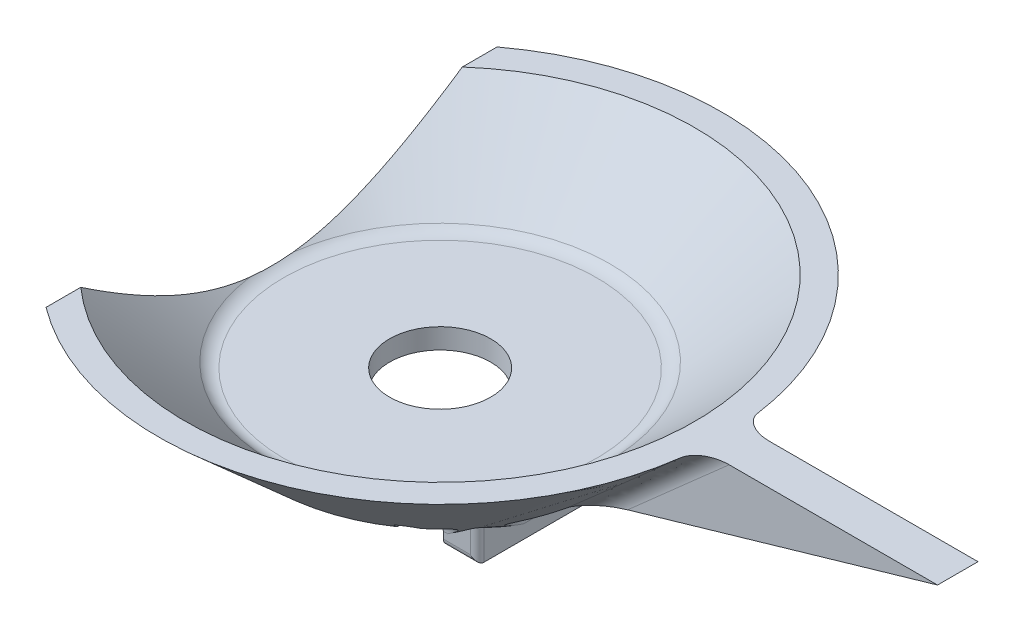
SolidWorks part; units mm, degrees
material "ABS"
ref_plane "前视基准面" through (0, 0, 0) normal (0, 0, 1) x (1, 0, 0)
ref_plane "上视基准面" through (0, 0, 0) normal (0, 1, 0) x (1, 0, 0)
ref_plane "右视基准面" through (0, 0, 0) normal (1, 0, 0) x (0, 0, -1)
other "Configuration Table"
sketch "草图1" plane through (0, 0, 0) normal (0, 1, 0) x (1, 0, 0)
  circle A0 centre (0, 0) radius 41.75
  circle A1 centre (0, 0) radius 37.75
  dimension "D1" = 4
  dimension "D2" = 83.5
ref_plane "基准面1" through (0, -15, 0) normal (0, 1, 0) x (1, 0, 0)
sketch "草图2" plane through (0, -15, 0) normal (0, 1, 0) x (1, 0, 0)
  circle A0 centre (0, 0) radius 25
  circle A1 centre (0, 0) radius 21
  dimension "D1" = 50
  dimension "D2" = 4
sketch "草图3" plane through (0, 0, 0) normal (0, 0, 1) x (1, 0, 0)
  line L0 (0, -15) -> (0, 0) construction
  line L1 (25, -15) -> (-25, -15) construction
  line L2 (41.75, 0) -> (37.75, 0)
  line L3 (41.75, 0) -> (-41.75, 0) construction
  line L4 (37.75, 0) -> (24.35, -12)
  line L5 (24.35, -12) -> (7.5, -12)
  line L6 (7.5, -12) -> (7.5, -15)
  line L7 (7.5, -15) -> (25, -15)
  line L8 (25, -15) -> (41.75, 0)
  dimension "D1" = 4
  dimension "D2" = 15
  dimension "D3" = 3
  dimension "D4" = 83.5
  dimension "D5" = 50
revolve "旋转1" add sketch "草图3" angle 360 about L0
sketch "草图4" plane through (0, 0, 0) normal (0, 0, 1) x (1, 0, 0)
  line L0 (41.75, 0) -> (76.75, 0)
  line L1 (76.75, 0) -> (25, -15)
  line L2 (25, -15) -> (22, -15)
  line L3 (-25, -15) -> (25, -15) construction
  line L4 (22, -15) -> (22, 0)
  line L5 (41.75, 0) -> (-41.75, 0) construction
  line L6 (22, 0) -> (41.75, 0)
  dimension "D1" = 3
  dimension "D2" = 35
extrude "凸台-拉伸1" add sketch "草图4" along normal mid plane 6
sketch "草图5" plane through (0, 0, 0) normal (0, 0, 1) x (1, 0, 0)
  line L15 (-24.35, -12) -> (-37.75, 0)
  line L16 (-24.35, -12) -> (-37.75, 0)
  line L17 (-37.75, 0) -> (0, 0)
  line L18 (0, 0) -> (0, -12)
  line L19 (0, -12) -> (-24.35, -12)
revolve "切除-旋转1" cut sketch "草图5" angle 360 about L18
fillet "圆角1" radius 3 3 edges at (0, -12, -24.35)
sketch "草图6" plane through (0, 0, 0) normal (0, 1, 0) x (1, 0, 0)
  line L0 (0, 0) -> (-25, 0) construction
  line L1 (-25, 45) -> (-25, -45)
  line L3 (-25, -45) -> (-45, -45)
  line L4 (-25, -45) -> (-25, 45)
  line L5 (-25, 45) -> (-45, 45)
  line L6 (-45, -45) -> (-45, 45)
  point P6 (-25, 0)
  circle M5 centre (0, 0) radius 37.75
  arc M6 (41.3555, 5.7255) -> (41.3555, -5.7255) centre (0, 0) ccw
  dimension "D1" = 25
  dimension "D2" = 90
  dimension "D3" = 20
extrude "切除-拉伸1" cut sketch "草图6" against normal through all contours L1 M6 M5 | L1 L4 M5 | L6 L3 L1 L5 M6 region at (-25.922, 0, -39.2187) region at (-25.6894, 0, -30.8614) region at (-30.1819, 0, 0)
sketch "草图7" plane through (0, -15, 0) normal (0, -1, 0) x (1, 0, 0)
  line L0 (0, 0) -> (0, 25) construction
  line L1 (-17.7, 0) -> (17.7, 0) construction
  line L3 (-20.2, 14.7296) -> (-15.2, 14.7296)
  line L4 (-20.2, 14.7296) -> (-20.2, -14.7296)
  line L5 (-20.2, -14.7296) -> (-15.2, -14.7296)
  line L6 (-15.2, 14.7296) -> (-15.2, -14.7296)
  line L7 (-20.2, 14.7296) -> (-15.2, -14.7296) construction
  line L8 (-20.2, -14.7296) -> (-15.2, 14.7296) construction
  line L9 (15.2, 14.7296) -> (20.2, 14.7296)
  line L10 (15.2, 14.7296) -> (15.2, -14.7296)
  line L11 (15.2, -14.7296) -> (20.2, -14.7296)
  line L12 (20.2, 14.7296) -> (20.2, -14.7296)
  line L13 (15.2, 14.7296) -> (20.2, -14.7296) construction
  line L14 (15.2, -14.7296) -> (20.2, 14.7296) construction
  arc A0 (24.375, 5.5553) -> (-25, 0) centre (0, 0) ccw construction
  point P9 (0, 0)
  point P18 (0, 0)
  dimension "D1" = 35.4
  dimension "D2" = 5
extrude "凸台-拉伸2" add sketch "草图7" along normal blind 5
sketch "草图8" plane through (0, 0, 14.7296) normal (0, 0, 1) x (1, 0, 0)
  circle A0 centre (-15.2, -15) radius 1
  circle A1 centre (15.2, -15) radius 1
  dimension "D1" = 2
extrude "切除-拉伸2" cut sketch "草图8" against normal through all both and the other way through all
fillet "圆角2" radius 3 6 edges at (20.2, -15, 0) (18.2, -15, -14.7296) (-18.2, -15, -14.7296) (-20.2, -15, 0) (18.2, -15, 14.7296) (-18.2, -15, 14.7296)
fillet "圆角3" radius 1 8 edges at (20.2, -17.5, -14.7296) (20.2, -17.5, 14.7296) (-20.2, -17.5, 14.7296) (-20.2, -17.5, -14.7296) (-17.7, -20, -14.7296) (17.7, -20, -14.7296) (17.7, -20, 14.7296) (-17.7, -20, 14.7296)
